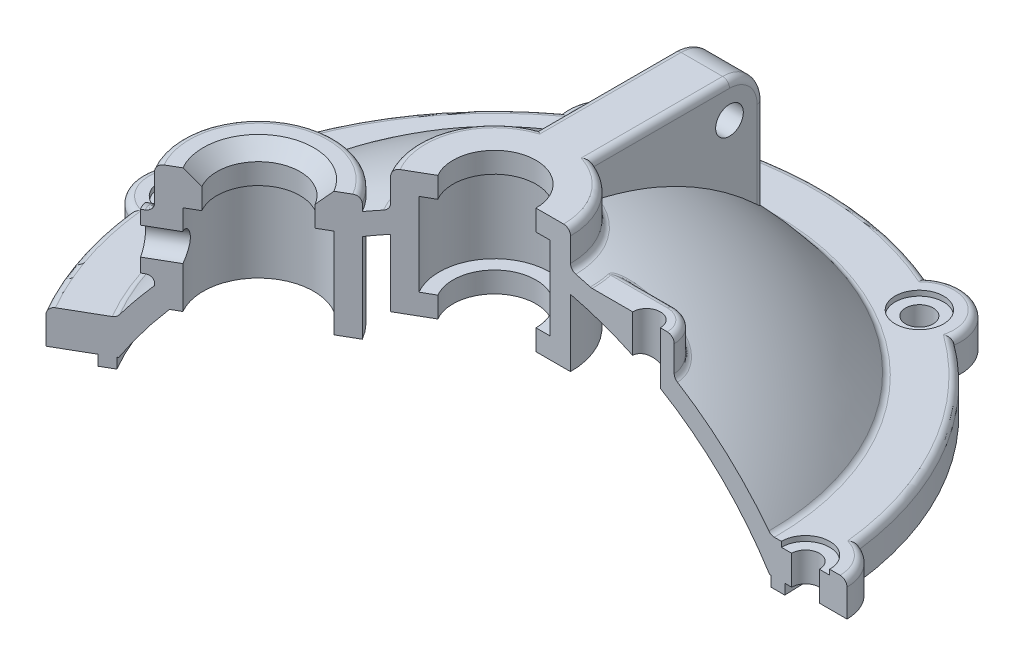
SolidWorks part; units mm, degrees
ref_plane "前基準面" through (0, 0, 0) normal (0, 0, 1) x (1, 0, 0)
ref_plane "上基準面" through (0, 0, 0) normal (0, 1, 0) x (1, 0, 0)
ref_plane "右基準面" through (0, 0, 0) normal (1, 0, 0) x (0, 0, -1)
ref_axis "基準軸1" through (0, 55, 0) along (0, -1, 0)
sketch "草圖8" plane through (0, 0, 0) normal (1, 0, 0) x (0, 0, -1)
  line L0 (-114.3443, 25) -> (96.5847, 25) construction
  line L1 (0, 55) -> (0, -55) construction
  line L2 (0, 0) -> (43.3013, 0)
  line L3 (0, 0) -> (0, 25)
  arc A0 (43.3013, 0) -> (0, 25) centre (0, -25) ccw
  dimension "D2" = 100
  dimension "D1" = 25
revolve "旋轉3" add sketch "草圖8" angle 360 about axis through (0, 55, 0) along (0, -1, 0)
sketch "草圖9" plane through (0, 0, 0) normal (0, -1, 0) x (1, 0, 0)
  circle A0 centre (0, 0) radius 47.5
  dimension "D1" = 95
extrude "填料-伸長3" add sketch "草圖9" against normal blind 5
sketch "草圖10" plane through (0, 0, 0) normal (0, -1, 0) x (1, 0, 0)
  circle A0 centre (0, 0) radius 42
  dimension "D1" = 84
extrude "填料-伸長4" add sketch "草圖10" along normal blind 1.5
sketch "草圖36" plane through (0, 0, 0) normal (0, 0, 1) x (1, 0, 0)
  line L0 (0, 0) -> (0, 22) construction
  line L1 (-47.5, 0) -> (47.5, 0) construction
  line L2 (39.7995, 0) -> (0, 0)
  line L3 (0, 0) -> (0, 22)
  line L4 (0, 25) -> (0, 34.8586) construction
  arc A0 (40, 5) -> (-40, 5) centre (0, -25) ccw construction
  arc A1 (43.3013, 0) -> (0, 25) centre (0, -25) ccw construction
  arc A2 (39.7995, 0) -> (0, 22) centre (0, -25) ccw
  arc A3 (40.7032, -1.5) -> (0, 22) centre (0, -25) ccw construction
  dimension "D1" = 3
revolve "除料-旋轉1" cut sketch "草圖36" angle 360 about L3
sketch "草圖37" plane through (0, -1.5, 0) normal (0, -1, 0) x (1, 0, 0)
  circle A0 centre (0, 0) radius 40
  dimension "D1" = 80
extrude "除料-伸長12" cut sketch "草圖37" against normal blind 1.5
sketch "草圖11" plane through (0, 5, 0) normal (0, 1, 0) x (1, 0, 0)
  line L0 (0, 0) -> (72.4947, 0) construction
  circle A0 centre (0, 0) radius 45 construction
  arc A1 (47.1694, -5.5941) -> (47.1694, 5.5941) centre (45, 0) ccw
  circle A2 centre (0, 0) radius 47.5 construction
  arc A4 (47.1694, -5.5941) -> (47.1694, 5.5941) centre (0, 0) ccw
  dimension "D1" = 90
  dimension "D2" = 12
extrude "填料-伸長5" add sketch "草圖11" against normal up to surface (5 mm away)
pattern_circular "環狀複製排列1" count 6 over 360 about axis through (0, 55, 0) along (0, -1, 0) of "填料-伸長5" reverse direction yes
sketch "草圖12" plane through (0, 5, 0) normal (0, 1, 0) x (1, 0, 0)
  circle A0 centre (45, 0) radius 3.5
  dimension "D1" = 7
extrude "除料-伸長1" cut sketch "草圖12" against normal blind 0.75
pattern_circular "環狀複製排列2" count 6 over 360 about axis through (0, 55, 0) along (0, -1, 0) of "除料-伸長1"
sketch "草圖13" plane through (0, 4.25, 0) normal (0, 1, 0) x (1, 0, 0)
  circle A0 centre (45, 0) radius 2
  dimension "D1" = 4
extrude "除料-伸長2" cut sketch "草圖13" against normal through all
pattern_circular "環狀複製排列3" count 6 over 360 about axis through (0, 55, 0) along (0, -1, 0) of "除料-伸長2"
ref_plane "平面1" through (0, 29, 0) normal (0, -1, 0) x (-1, 0, 0)
sketch "草圖14" plane through (0, 29, 0) normal (0, -1, 0) x (-1, 0, 0)
  circle A0 centre (0, 0) radius 11
  dimension "D1" = 22
extrude "填料-伸長6" add sketch "草圖14" along normal blind 18
sketch "草圖15" plane through (0, 29, 0) normal (0, 1, 0) x (1, 0, 0)
  circle A0 centre (0, 0) radius 6
  dimension "D1" = 12
extrude "除料-伸長3" cut sketch "草圖15" against normal blind 3
sketch "草圖16" plane through (0, 26, 0) normal (0, 1, 0) x (1, 0, 0)
  circle A0 centre (0, 0) radius 8
  dimension "D1" = 16
extrude "除料-伸長4" cut sketch "草圖16" against normal blind 12
sketch "草圖17" plane through (0, 14, 0) normal (0, 1, 0) x (1, 0, 0)
  circle A0 centre (0, 0) radius 6
  dimension "D1" = 12
extrude "除料-伸長5" cut sketch "草圖17" against normal blind 3
sketch "草圖18" plane through (0, 29, 0) normal (0, 1, 0) x (1, 0, 0)
  line L0 (-4, -10.247) -> (-4, -35)
  line L1 (-4, -35) -> (4, -35)
  line L2 (4, -35) -> (4, -10.247)
  line L3 (0, 0) -> (0, -48.5571) construction
  circle A0 centre (0, 0) radius 11 construction
  arc A4 (-4, -10.247) -> (4, -10.247) centre (0, 0) ccw
  point P9 (-4, -35)
  point P12 (4, -35)
  dimension "D5" = 11
  dimension "D1" = 8
  dimension "D2" = 4
  dimension "D3" = 35
extrude "填料-伸長8" add sketch "草圖18" against normal up to next
fillet "圓角3" radius 5 1 edges at (0, 29, 35)
sketch "草圖21" plane through (4, 0, 0) normal (1, 0, 0) x (0, 0, -1)
  circle A0 centre (-30, 24) radius 2
  dimension "D1" = 4
extrude "除料-伸長6" cut sketch "草圖21" against normal through all
ref_axis "基準軸2" through (52.25, 5, 0) along (-1, 0, 0)
mirror "鏡射1" about plane through (0, 0, 0) normal (0, 0, 1) of "除料-伸長6", "圓角3", "填料-伸長8"
ref_plane "平面2" through (0, 0, 0) normal (-0.5, 0, -0.866) x (0, -1, 0)
ref_plane "平面3" through (0, 25, 0) normal (0, -1, 0) x (-1, 0, 0)
sketch "草圖22" plane through (0, 25, 0) normal (0, -1, 0) x (-1, 0, 0)
  line L0 (52.3945, -30.25) -> (-52.3945, 30.25) construction
  circle A0 centre (21.6506, -12.5) radius 11
  dimension "D1" = 22
  dimension "D2" = 25
extrude "填料-伸長9" add sketch "草圖22" along normal blind 18
sketch "草圖23" plane through (0, 25, 0) normal (0, 1, 0) x (1, 0, 0)
  circle A0 centre (-21.6506, -12.5) radius 8
  dimension "D1" = 16
extrude "除料-伸長7" cut sketch "草圖23" against normal blind 2
chamfer "導角1" distance 2 angle 45 1 edges at (-21.6506, 23, 20.5)
sketch "草圖25" plane through (0, 23, 0) normal (0, 1, 0) x (1, 0, 0)
  circle A1 centre (-21.6506, -12.5) radius 6
  circle A2 centre (-21.6506, -12.5) radius 6
  dimension "D1" = 0
extrude "除料-伸長8" cut sketch "草圖25" against normal blind 3
sketch "草圖26" plane through (0, 20, 0) normal (0, 1, 0) x (1, 0, 0)
  circle A0 centre (-21.6506, -12.5) radius 8
  dimension "D1" = 16
extrude "除料-伸長9" cut sketch "草圖26" against normal blind 13
ref_plane "平面6" through (0, 0, 0) normal (-0.5, 0, -0.866) x (0, -1, 0)
ref_plane "平面7" through (0, 0, 0) normal (0.866, 0, -0.5) x (0, -1, 0)
ref_plane "平面8" through (-51.9615, 0, 30) normal (0.866, 0, -0.5) x (0, -1, 0)
sketch "草圖29" plane through (0, 29, 0) normal (0, 1, 0) x (1, 0, 0)
  line L0 (0, 0) -> (-56.536, -32.6411) construction
  line L1 (52.25, 0) -> (-52.25, 0) construction
  dimension "D1" = 30
sketch "草圖30" plane through (-51.9615, 0, 30) normal (0.866, 0, -0.5) x (0, -1, 0)
  line L0 (-29, 0) -> (-38.7139, 0) construction
  line L1 (-29, 0) -> (-6.7183, 0) construction
  line L2 (-25, 11) -> (-25, -11) construction
  circle A0 centre (-15, 0) radius 4
  dimension "D1" = 8
  dimension "D2" = 10
extrude "填料-伸長10" add sketch "草圖30" along normal up to next from offset 22.5
sketch "草圖31" plane through (-32.476, 0, 18.75) normal (-0.866, 0, 0.5) x (0.5, 0, 0.866)
  circle A0 centre (0, 15) radius 2
  dimension "D1" = 4
extrude "除料-伸長10" cut sketch "草圖31" against normal up to next
ref_plane "平面9" through (0, 23, 0) normal (0, -1, 0) x (-1, 0, 0)
sketch "草圖32" plane through (0, 23, 0) normal (0, -1, 0) x (-1, 0, 0)
  line L1 (-22, -4) -> (-10.247, -4)
  line L2 (-52.25, 0) -> (52.25, 0) construction
  line L3 (-10.247, 4) -> (-22, 4)
  line L5 (0, 0) -> (-83.0928, 0) construction
  arc A0 (-4, 10.247) -> (-4, -10.247) centre (0, 0) ccw construction
  arc A1 (-10.247, 4) -> (-10.247, -4) centre (0, 0) ccw
  arc A2 (-22, 4) -> (-22, -4) centre (-22, 0) ccw
  dimension "D2" = 22
  dimension "D1" = 8
extrude "填料-伸長11" add sketch "草圖32" along normal up to surface up to face at (0, 5, -40)
sketch "草圖33" plane through (0, 23, 0) normal (0, 1, 0) x (1, 0, 0)
  circle A0 centre (22, 0) radius 2
  dimension "D1" = 4
extrude "除料-伸長11" cut sketch "草圖33" against normal blind 8
fillet "圓角4" radius 1 13 edges at (-51, 5, 0) (-41.1362, 5, 23.75) (-41.1362, 5, -23.75) (-25.5, 5, -44.1673) (0, 5, -47.5) (25.5, 5, -44.1673) (41.1362, 5, -23.75) (51, 5, 0) (41.1362, 5, 23.75) (25.5, 5, 44.1673) (0, 5, 47.5) (-25.5, 5, 44.1673) (0, 5, -40)
fillet "圓角5" radius 1 7 edges at (14, 23, 0) (17.7839, 21.5589, -4) (17.7839, 21.5589, 4) (17.7082, 23, -4) (17.7082, 23, 4) (25.9156, 17.7518, 0.8173) (26, 23, 0)
fillet "圓角6" radius 1 10 edges at (4, 29, 20.1235) (4, 27.5355, 33.5355) (-4, 29, 20.1235) (-4, 27.5355, 33.5355) (4, 17.2412, 35) (-4, 17.2412, 35) (-11, 29, 0) (-11, 23.775, 0) (11, 23.775, 0) (11, 29, 0)
fillet "圓角7" radius 1 8 edges at (-4, 17.2412, -35) (-4, 27.5355, -33.5355) (4, 17.2412, -35) (4, 27.5355, -33.5355) (-4, 29, -19.5826) (4, 29, -19.5826) (-21.6506, 25, 1.5) (-32.5162, 14.3581, 14.2143)
sketch "草圖38" plane through (0, 0, 0) normal (0, 1, 0) x (1, 0, 0)
  line L0 (0, 0) -> (56.0566, 0)
  line L1 (0, 0) -> (-52.4414, -30.2771)
  line L2 (-52.4414, -30.2771) -> (-51.1765, -52.5892)
  line L3 (-51.1765, -52.5892) -> (56.0566, -50.1492)
  line L4 (56.0566, -50.1492) -> (56.0566, 0)
extrude "除料-伸長14" cut sketch "草圖38" along normal through all from offset 30 offset against normal yes
